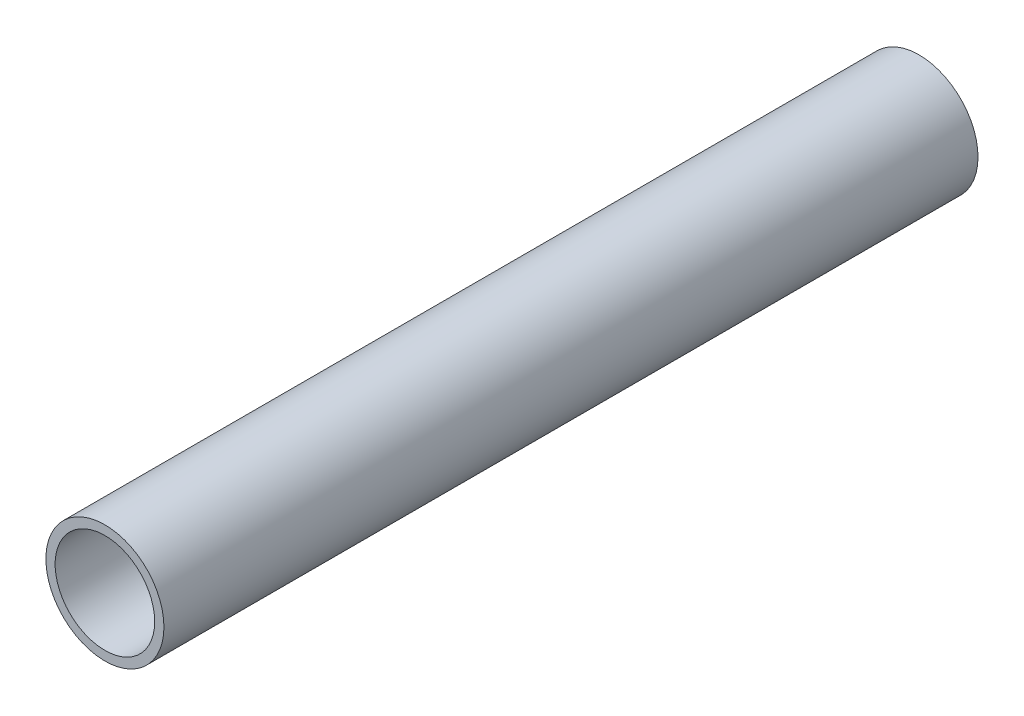
SolidWorks part; units mm, degrees
ref_plane "Front Plane" through (0, 0, 0) normal (0, 0, 1) x (1, 0, 0)
ref_plane "Top Plane" through (0, 0, 0) normal (0, 1, 0) x (1, 0, 0)
ref_plane "Right Plane" through (0, 0, 0) normal (1, 0, 0) x (0, 0, -1)
sketch "Sketch1" plane through (0, 0, 0) normal (0, 0, 1) x (1, 0, 0)
  line L0 (-7.9375, 0) -> (7.9375, 0) construction
  line L1 (0, -7.9375) -> (0, 7.9375) construction
  circle A0 centre (0, 0) radius 7.9375
  circle A1 centre (0, 0) radius 6.6929
  point P4 (0, 0)
  point P9 (0, 0)
  point P10 (6.6929, 0)
  dimension "ID" = 13.3858
  dimension "OD" = 15.875
  dimension "Wall Thickness" = 1.2446
sketch "Sketch2" plane through (0, 0, 0) normal (1, 0, 0) x (0, 0, -1)
  line L0 (54.7364, 7.9375) -> (-54.7364, 7.9375) construction
  line L1 (0, 7.9375) -> (0, -7.9375) construction
  point P3 (-36.4801, 7.9375)
  point P4 (0, 7.9375)
  point P5 (36.4801, 7.9375)
  dimension "Length" = 109.4728
  dimension "D1" = 18.2563
  dimension "D2" = 18.2562
sketch "Sketch3" plane through (0, 0, 0) normal (0, 0, 1) x (1, 0, 0)
  line L0 (0, -7.9375) -> (0, 7.9375) construction
  circle A0 centre (0, 0) radius 7.9375
  circle A1 centre (0, 0) radius 6.6929
  circle A2 centre (0, 0) radius 6.6929 construction
extrude "Boss-Extrude1" add sketch "Sketch3" along normal mid plane 109.4728
equation "\"D1@Boss-Extrude1\" = \"Length@Sketch2\""
equation "\"D1@Sketch2\"=\"OD@Sketch1\"*1.15"
equation "\"D2@Sketch2\"=\"D1@Sketch2\""
